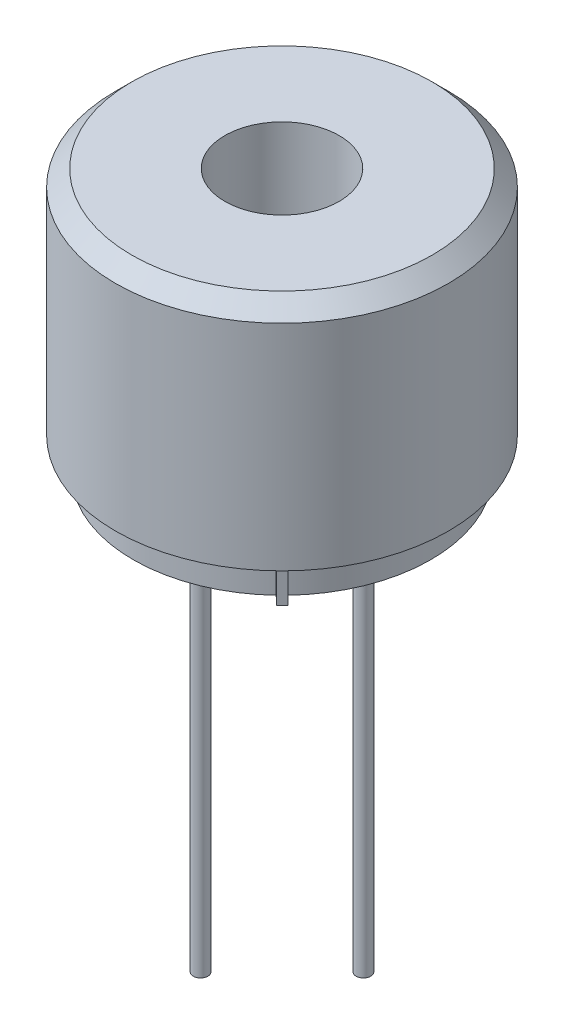
SolidWorks part; units mm, degrees
ref_plane "Front Plane" through (0, 0, 0) normal (0, 0, 1) x (1, 0, 0)
ref_plane "Top Plane" through (0, 0, 0) normal (0, 1, 0) x (1, 0, 0)
ref_plane "Right Plane" through (0, 0, 0) normal (1, 0, 0) x (0, 0, -1)
sketch "Sketch1" plane through (0, 0, 0) normal (0, 1, 0) x (1, 0, 0)
  circle A0 centre (0, 0) radius 5.1
  circle A1 centre (0, 0) radius 4.6
  circle A2 centre (0, 0) radius 1.75
  circle A3 centre (0, 0) radius 0.75
  dimension "D1" = 10.2
  dimension "D2" = 0.5
  dimension "D3" = 3.5
  dimension "D4" = 1.5
extrude "Boss-Extrude1" add sketch "Sketch1" against normal blind 7.07 contours A0 A1 | A1 A2 | A2 A3 | A3 region at (-4.9558, 0, 0) region at (-4.4699, 0, 0) region at (-1.7005, 0, 0) region at (0, 0, 0)
extrude "Cut-Extrude1" cut sketch "Sketch1<5>" against normal blind 5.74 contours A3 region at (0, 0, 0)
sketch "Sketch1<5>" plane through (0, 0, 0) normal (0, 1, 0) x (1, 0, 0) same geometry as "Sketch1"
extrude "Cut-Extrude2" cut sketch "Sketch1<6>" against normal blind 4 contours A2 A3 region at (-1.7005, 0, 0)
sketch "Sketch1<6>" plane through (0, 0, 0) normal (0, 1, 0) x (1, 0, 0) same geometry as "Sketch1"
chamfer "Chamfer1" distance 0.5 angle 45 1 edges at (0, 0, 5.1)
sketch "Sketch2" plane through (0, -7.07, 0) normal (0, -1, 0) x (1, 0, 0)
  line L0 (0, 5.1) -> (0, -5.1)
  line L1 (-5.1, 0) -> (5.1, 0)
  circle A0 centre (0, 0) radius 4.56
  circle A1 centre (0, 0) radius 5.1 construction
  circle A2 centre (0, 2.4946) radius 0.8
  circle A3 centre (0, 2.4946) radius 0.225
  circle A4 centre (2.4946, 0) radius 0.8
  circle A5 centre (2.4946, 0) radius 0.225
  circle A6 centre (0, -2.4946) radius 0.8
  circle A7 centre (0, -2.4946) radius 0.225
  circle A8 centre (-2.4946, 0) radius 0.8
  circle A9 centre (-2.4946, 0) radius 0.225
  arc A10 (4.56, 0) -> (3.2016, 3.247) centre (0, 0) ccw
  point P0 (0, 0)
  point P9 (0, 0)
  point P13 (0, 0)
  point P28 (0, 0)
  point P29 (-0.0484, 0)
  dimension "D1" = 9.12
  dimension "D2" = 1.6
  dimension "D3" = 0.45
  dimension "D4" = 4
extrude "Boss-Extrude3" add sketch "Sketch2" along normal blind 1.03 contours L1 A9 | L1 A9 | A9 L1 A8 | A9 L1 A8 | A7 L0 A6 | L0 A7 | L0 A7 | A7 L0 A6 | L0 A3 | L0 A3 | A3 L0 A2 | A3 L0 A2 | L1 A5 | L1 A5 | A5 L1 A4 | A5 L1 A4 | A8 L1 L0 A2 A0 | A8 L1 A0 L0 A6 | A6 L0 A0 L1 A4 | A4 L1 A0 L0 A2 region at (2.0081, -7.07, 2.0081) region at (-2.0081, -7.07, 2.0081) region at (0.3605, -7.07, 2.4946) region at (-0.3605, -7.07, 2.4946) region at (-2.0081, -7.07, -2.0081) region at (0.0955, -7.07, 2.4946) region at (-0.0955, -7.07, 2.4946) region at (2.0081, -7.07, -2.0081) region at (-2.4946, -7.07, 0.3605) region at (-2.4946, -7.07, -0.3605) region at (2.4946, -7.07, -0.3605) region at (2.4946, -7.07, 0.3605) region at (-2.4946, -7.07, 0.0955) region at (-2.4946, -7.07, -0.0955) region at (-0.3605, -7.07, -2.4946) region at (0.3605, -7.07, -2.4946) region at (2.4946, -7.07, -0.0955) region at (2.4946, -7.07, 0.0955) region at (-0.0955, -7.07, -2.4946) region at (0.0955, -7.07, -2.4946)
extrude "Boss-Extrude4" add sketch "Sketch2<3>" along normal blind 1.1 contours A9 L1 A8 | A9 L1 A8 | L1 A9 | L0 A7 | L0 A7 | A7 L0 A6 | A7 L0 A6 | L1 A5 | L1 A5 | A5 L1 A4 | A5 L1 A4 | L0 A3 | L0 A3 | A3 L0 A2 | A3 L0 A2 | A9 region at (0.3605, -7.07, 2.4946) region at (-0.3605, -7.07, 2.4946) region at (0.0955, -7.07, 2.4946) region at (-0.0955, -7.07, 2.4946) region at (-2.4946, -7.07, 0.3605) region at (-2.4946, -7.07, -0.3605) region at (2.4946, -7.07, -0.3605) region at (2.4946, -7.07, 0.3605) region at (-2.4946, -7.07, 0.0955) region at (-0.3605, -7.07, -2.4946) region at (0.3605, -7.07, -2.4946) region at (2.4946, -7.07, -0.0955) region at (2.4946, -7.07, 0.0955) region at (-0.0955, -7.07, -2.4946) region at (0.0955, -7.07, -2.4946)
sketch "Sketch2<3>" plane through (0, -7.07, 0) normal (0, -1, 0) x (1, 0, 0) same geometry as "Sketch2"
extrude "Boss-Extrude5" add sketch "Sketch2<4>" along normal blind 13 contours L1 A9 | L1 A9 | L0 A3 | L0 A3 | L1 A5 | L1 A5 | L0 A7 | L0 A7 region at (0.0955, -7.07, 2.4946) region at (-0.0955, -7.07, 2.4946) region at (-2.4946, -7.07, 0.0955) region at (-2.4946, -7.07, -0.0955) region at (2.4946, -7.07, -0.0955) region at (2.4946, -7.07, 0.0955) region at (-0.0955, -7.07, -2.4946) region at (0.0955, -7.07, -2.4946)
sketch "Sketch2<4>" plane through (0, -7.07, 0) normal (0, -1, 0) x (1, 0, 0) same geometry as "Sketch2"
sketch "Sketch4" plane through (0, -8.1, 0) normal (0, -1, 0) x (1, 0, 0)
  line L0 (0, 4.56) -> (0, -4.56)
  line L1 (0, 0) -> (3.2244, 3.2244)
  line L2 (-4.56, 0) -> (4.56, 0)
  line L3 (2.862, 3.0505) -> (3.0365, 2.8691)
  line L4 (2.862, 3.0505) -> (3.4123, 3.5798)
  line L5 (3.0365, 2.8691) -> (3.5868, 3.3984)
  line L6 (3.4123, 3.5798) -> (3.5868, 3.3984)
  line L7 (2.862, 3.0505) -> (3.5868, 3.3984) construction
  line L8 (3.0365, 2.8691) -> (3.4123, 3.5798) construction
  circle A0 centre (0, 0) radius 4.56 construction
  point P6 (0, 0)
  point P13 (0, 0)
  circle M11 centre (0, 0) radius 4.56
  dimension "D1" = 45
extrude "Boss-Extrude6" add sketch "Sketch4" against normal up to surface (1.03 mm away) contours L6 L4 L5 M11 region at (3.3616, -8.1, 3.3567) up to face at (0, -7.07, -4.56)
